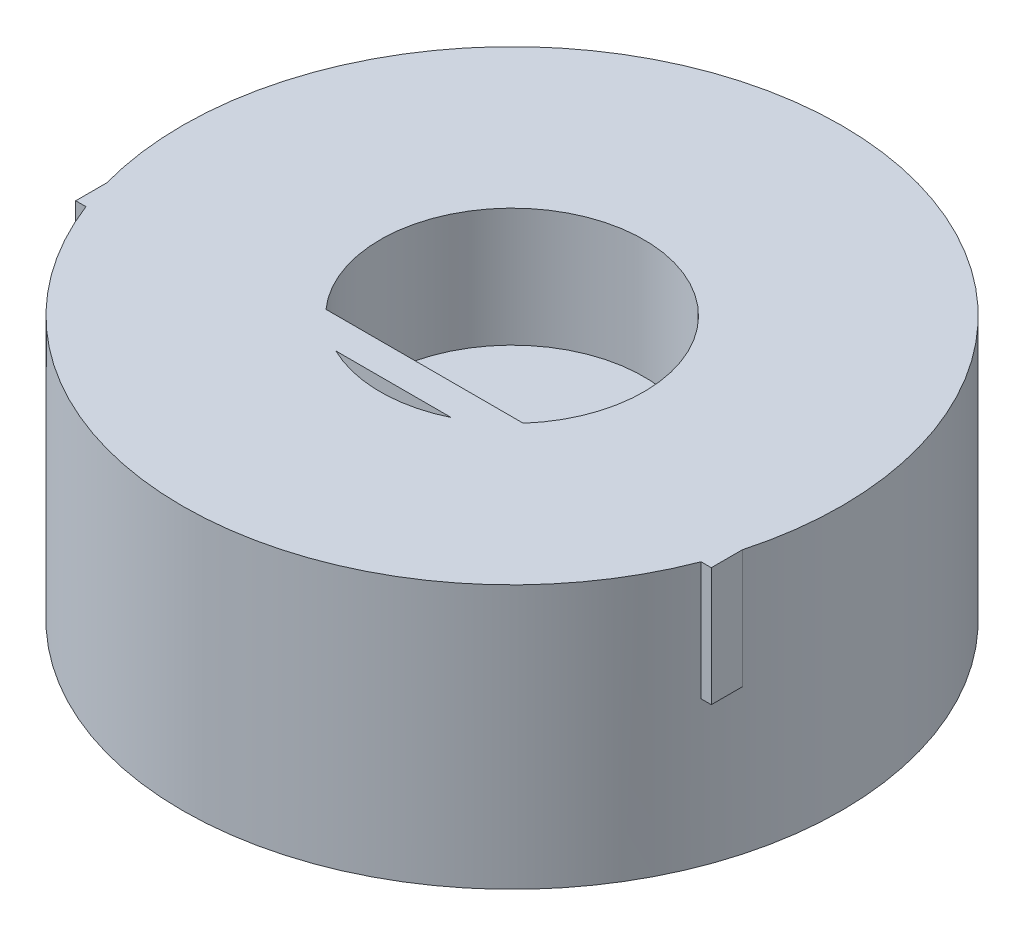
SolidWorks part; units mm, degrees
ref_plane "Front Plane" through (0, 0, 0) normal (0, 0, 1) x (1, 0, 0)
ref_plane "Top Plane" through (0, 0, 0) normal (0, 1, 0) x (1, 0, 0)
ref_plane "Right Plane" through (0, 0, 0) normal (1, 0, 0) x (0, 0, -1)
sketch "Sketch1" plane through (0, 0, 0) normal (0, 1, 0) x (1, 0, 0)
  circle A0 centre (0, 0) radius 25
  dimension "D1" = 50
extrude "Boss-Extrude1" add sketch "Sketch1" along normal blind 20
sketch "Sketch2" plane through (0, 20, 0) normal (0, 1, 0) x (1, 0, 0)
  circle A0 centre (0, 0) radius 10
  dimension "D1" = 20
extrude "Cut-Extrude5" cut sketch "Sketch2" against normal blind 9
sketch "Sketch9" plane through (0, 11, 0) normal (0, 1, 0) x (1, 0, 0)
  line L5 (-24.103, -8.9925) -> (24.103, -8.9925)
  line L6 (-24.103, -8.9925) -> (-24.103, -6.6366)
  line L7 (-24.103, -6.6366) -> (24.103, -6.6366)
  line L8 (24.103, -8.9925) -> (24.103, -6.6366)
  line L9 (-24.103, -8.9925) -> (24.103, -6.6366) construction
  line L10 (-24.103, -6.6366) -> (24.103, -8.9925) construction
  circle A0 centre (0, 0) radius 25 construction
  point P0 (0, -7.8145)
extrude "Boss-Extrude7" add sketch "Sketch9" along normal blind 9
sketch "Sketch21" plane through (0, 0, 0) normal (0, 0, 1) x (1, 0, 0)
  line L0 (-0.108, 20) -> (-0.108, 0) construction
  line L1 (25, 20) -> (-25, 20) construction
  line L2 (25, 0) -> (-25, 0) construction
